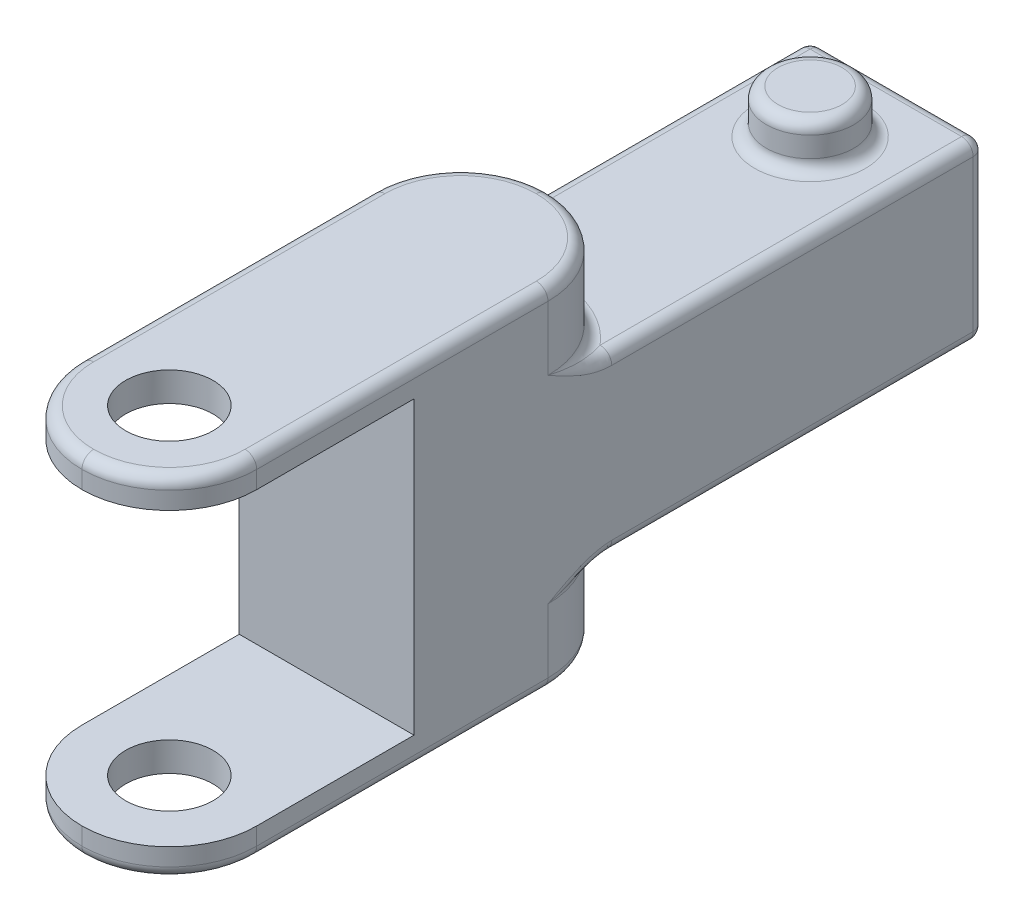
SolidWorks part; units mm, degrees
ref_plane "Front Plane" through (0, 0, 0) normal (0, 0, 1) x (1, 0, 0)
ref_plane "Top Plane" through (0, 0, 0) normal (0, 1, 0) x (1, 0, 0)
ref_plane "Right Plane" through (0, 0, 0) normal (1, 0, 0) x (0, 0, -1)
sketch "Sketch1" plane through (0, 0, 0) normal (0, 0, 1) x (1, 0, 0)
  line L1 (-15, 15) -> (15, 15)
  line L2 (-15, 15) -> (-15, -15)
  line L3 (-15, -15) -> (15, -15)
  line L4 (15, 15) -> (15, -15)
  line L5 (-15, 15) -> (15, -15) construction
  line L6 (-15, -15) -> (15, 15) construction
  point P0 (0, 0)
  dimension "D1" = 30
  dimension "D2" = 30
extrude "Boss-Extrude1" add sketch "Sketch1" along normal blind 100
sketch "Sketch2" plane through (0, 0, 100) normal (0, 0, 1) x (1, 0, 0)
  line L0 (-15, -15) -> (15, -15) construction
  line L1 (-15, 30) -> (15, 30)
  line L2 (-15, 30) -> (-15, -30)
  line L3 (-15, -30) -> (15, -30)
  line L4 (15, 30) -> (15, -30)
  line L5 (-15, 30) -> (15, -30) construction
  line L6 (-15, -30) -> (15, 30) construction
  point P0 (0, 0)
  line M2 (15, 15) -> (-15, 15)
  line M4 (-15, -15) -> (15, -15)
  dimension "D1" = 60
extrude "Boss-Extrude2" add sketch "Sketch2" along normal mid plane 80 contours L4 L1 L2 M2 | L4 L2 L3 M4 region at (0, 22.5, 100) region at (0, -22.5, 100)
fillet "Fillet1" radius 15 4 edges at (15, 22.5, 60) (-15, 22.5, 140) (-15, 22.5, 60) (15, 22.5, 140)
fillet "Fillet2" radius 15 4 edges at (-15, -22.5, 60) (-15, -22.5, 140) (15, -22.5, 60) (15, -22.5, 140)
sketch "Sketch3" plane through (0, 30, 0) normal (0, 1, 0) x (1, 0, 0)
  circle A0 centre (0, -125) radius 7.5
  dimension "D1" = 15
extrude "Cut-Extrude1" cut sketch "Sketch3" against normal up to surface (60 mm away) up to face at (0, -30, 100)
sketch "Sketch4" plane through (0, 0, 0) normal (0, 1, 0) x (1, 0, 0)
  line L0 (0, 0) -> (0, -15) construction
  circle A0 centre (0, -15) radius 7.5
  dimension "D2" = 15
  dimension "D1" = 15
extrude "Boss-Extrude3" add sketch "Sketch4" along normal mid plane 45
fillet "Fillet3" radius 2 38 edges at (10.6066, 15, 135.6066) (-10.6066, 15, 135.6066) (-15, 15, 112.5) (-15, 0, 100) (-15, -15, 112.5) (-10.6066, -15, 135.6066) (10.6066, -15, 135.6066) (15, -15, 112.5) (15, 0, 100) (15, 15, 112.5) (-10.6066, -30, 64.3934) (10.6066, -30, 64.3934) (15, -30, 100) (10.6066, -30, 135.6066) (-10.6066, -30, 135.6066) (-15, -30, 100) (10.6066, 30, 64.3934) (-10.6066, 30, 64.3934) (-15, 30, 100) (-10.6066, 30, 135.6066) (10.6066, 30, 135.6066) (15, 30, 100) (10.6066, -15, 64.3934) (-10.6066, -15, 64.3934) (-15, 0, 0) (-15, 15, 37.5) (-10.6066, 15, 64.3934) (10.6066, 15, 64.3934) (15, 15, 37.5) (15, 0, 0) (15, -15, 37.5) (-15, -15, 37.5) (0, 22.5, 22.5) (0, 15, 7.5) (0, -15, 22.5) (0, -22.5, 22.5) (0, 15, 0) (0, -15, 0)
sketch "Sketch5" plane through (15, 0, 0) normal (1, 0, 0) x (0, 0, -1)
  line L0 (-98, 0) -> (-140, 0) construction
  line L1 (-140, 25) -> (-98, 25)
  line L2 (-140, 25) -> (-140, -25)
  line L3 (-140, -25) -> (-98, -25)
  line L4 (-98, 25) -> (-98, -25)
  line L5 (-140, 25) -> (-98, -25) construction
  line L6 (-140, -25) -> (-98, 25) construction
  line L7 (-98, 17) -> (-98, -17) construction
  line L8 (-140, 17) -> (-140, 28) construction
  point P0 (-119, 0)
  point P10 (0, 0)
  dimension "D1" = 50
extrude "Cut-Extrude2" cut sketch "Sketch5" against normal through all
